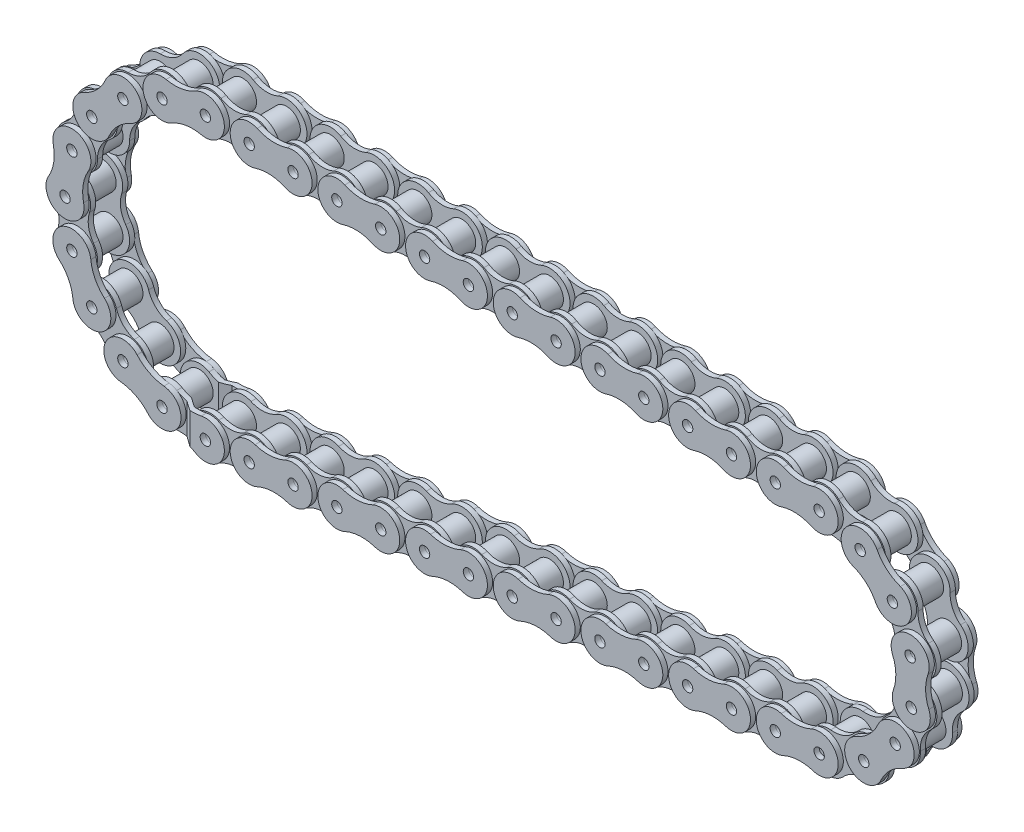
SolidWorks part; units mm, degrees
material "SUS304"
ref_plane "Front Plane" through (0, 0, 0) normal (0, 0, 1) x (1, 0, 0)
ref_plane "Top Plane" through (0, 0, 0) normal (0, 1, 0) x (1, 0, 0)
ref_plane "Right Plane" through (0, 0, 0) normal (1, 0, 0) x (0, 0, -1)
sketch "Sketch1" plane through (0, 0, 0) normal (0, 0, 1) x (1, 0, 0)
  line L0 (2.3431, 40.5223) -> (175.8629, 30.4891)
  line L1 (175.8629, -30.4891) -> (2.3431, -40.5223)
  line L2 (0, 0) -> (174.1, 0) construction
  arc A0 (2.3431, 40.5223) -> (2.3431, -40.5223) centre (0, 0) ccw
  arc A1 (175.8629, -30.4891) -> (175.8629, 30.4891) centre (174.1, 0) ccw
  dimension "D1" = 81.18
  dimension "D2" = 61.08
  dimension "D3" = 174.1
sketch "Sketch4" plane through (0, 0, 0) normal (0, 0, 1) x (1, 0, 0)
  line L1 (2.3431, 40.5223) -> (175.8629, 30.4891) construction
  line L3 (0, 0) -> (35.7842, 0) construction
  line L4 (0, 0) -> (174.1, 0) construction
  circle A0 centre (0, -40.59) radius 4
  arc A1 (2.3431, 40.5223) -> (2.3431, -40.5223) centre (0, 0) ccw construction
  circle A2 centre (-12.543, -38.6034) radius 4
  circle A3 centre (-23.8582, -32.838) radius 4
  circle A4 centre (-32.838, -23.8582) radius 4
  circle A5 centre (-38.6034, -12.543) radius 4
  circle A6 centre (-40.59, 0) radius 4
  circle A7 centre (-38.6034, 12.543) radius 4
  circle A8 centre (-32.838, 23.8582) radius 4
  circle A9 centre (-23.8582, 32.838) radius 4
  circle A10 centre (-12.543, 38.6034) radius 4
  circle A11 centre (0, 40.59) radius 4
  circle A12 centre (12.6782, 39.8618) radius 4
  circle A13 centre (25.3564, 39.1335) radius 4
  circle A14 centre (38.0345, 38.4053) radius 4
  circle A15 centre (50.7127, 37.6771) radius 4
  circle A16 centre (63.3909, 36.9488) radius 4
  circle A17 centre (76.0691, 36.2206) radius 4
  circle A18 centre (88.7473, 35.4924) radius 4
  circle A19 centre (101.4254, 34.7641) radius 4
  circle A20 centre (114.1036, 34.0359) radius 4
  circle A21 centre (126.7818, 33.3077) radius 4
  circle A22 centre (139.46, 32.5794) radius 4
  circle A23 centre (152.1382, 31.8512) radius 4
  circle A24 centre (164.8163, 31.123) radius 4
  circle A25 centre (177.4945, 30.3947) radius 4
  circle A26 centre (189.3571, 26.5029) radius 4
  circle A27 centre (198.6735, 18.192) radius 4
  circle A28 centre (203.8891, 6.8491) radius 4
  circle A29 centre (204.1336, -5.6332) radius 4
  circle A30 centre (199.3662, -17.1717) radius 4
  circle A31 centre (190.3823, -25.841) radius 4
  circle A34 centre (164.8163, -31.123) radius 4
  circle A35 centre (152.1382, -31.8512) radius 4
  circle A36 centre (139.46, -32.5794) radius 4
  circle A37 centre (126.7818, -33.3077) radius 4
  circle A38 centre (114.1036, -34.0359) radius 4
  circle A39 centre (101.4254, -34.7641) radius 4
  circle A40 centre (88.7473, -35.4924) radius 4
  circle A41 centre (76.0691, -36.2206) radius 4
  circle A42 centre (63.3909, -36.9488) radius 4
  circle A43 centre (50.7127, -37.6771) radius 4
  circle A44 centre (38.0345, -38.4053) radius 4
  circle A45 centre (25.3564, -39.1335) radius 4
  circle A46 centre (12.6782, -39.8618) radius 4
  circle A47 centre (0, -40.59) radius 4
  circle A48 centre (178.6813, -30.1944) radius 4
  arc A49 (175.8629, -30.4891) -> (175.8629, 30.4891) centre (174.1, 0) ccw construction
  dimension "D1" = 12.6993
  dimension "D3" = 8
  dimension "D5" = 12.6991
  dimension "D2" = 11
  dimension "D4" = 15
extrude "Boss-Extrude1" add sketch "Sketch4" along normal mid plane 7.8 contours A10 | A11 | A20 | A21 | A35 | A38 | A39 | A46 | A12 | A13 | A14 | A15 | A16 | A17 | A18 | A19 | A22 | A23 | A24 | A25 | A34 | A36 | A37 | A40 | A41 | A42 | A43 | A44 | A45 | A0 | A2 | A3 | A4 | A5 | A6 | A7 | A8 | A9 | A26 | A27 | A28 | A29 | A30 | A31 | A48 region at (-12.543, 38.6034, 0) region at (0, 40.59, 0) region at (114.1036, 34.0359, 0) region at (126.7818, 33.3077, 0) region at (152.1382, -31.8512, 0) region at (114.1036, -34.0359, 0) region at (101.4254, -34.7641, 0) region at (12.6782, -39.8618, 0)
sketch "Sketch5" plane through (0, 0, 3.9) normal (0, 0, 1) x (1, 0, 0)
  line L0 (0, 40.59) -> (12.6782, 39.8618) construction
  line L1 (25.3564, 39.1335) -> (38.0345, 38.4053) construction
  line L2 (50.7127, 37.6771) -> (63.3909, 36.9488) construction
  line L3 (76.0691, 36.2206) -> (88.7473, 35.4924) construction
  line L4 (101.4254, 34.7641) -> (114.1036, 34.0359) construction
  line L5 (126.7818, 33.3077) -> (139.46, 32.5794) construction
  line L6 (152.1382, 31.8512) -> (164.8163, 31.123) construction
  line L7 (0, 0) -> (224.3217, 0) construction
  line L8 (152.1382, -31.8512) -> (164.8163, -31.123) construction
  line L9 (126.7818, -33.3077) -> (139.46, -32.5794) construction
  line L10 (101.4254, -34.7641) -> (114.1036, -34.0359) construction
  line L11 (76.0691, -36.2206) -> (88.7473, -35.4924) construction
  line L12 (50.7127, -37.6771) -> (63.3909, -36.9488) construction
  line L13 (25.3564, -39.1335) -> (38.0345, -38.4053) construction
  line L14 (0, -40.59) -> (12.6782, -39.8618) construction
  line L15 (189.3571, 26.5029) -> (177.4945, 30.3947) construction
  line L16 (203.8891, 6.8491) -> (198.6735, 18.192) construction
  line L17 (199.3662, -17.1717) -> (204.1336, -5.6332) construction
  line L18 (178.6813, -30.1944) -> (190.3823, -25.841) construction
  arc A0 (2.9917, 45.6753) -> (2.3897, 35.1956) centre (0, 40.59) ccw
  arc A1 (9.6865, 34.7765) -> (10.2885, 45.2561) centre (12.6782, 39.8618) ccw
  arc A2 (2.9917, 45.6753) -> (10.2885, 45.2561) centre (7.0482, 52.5705) ccw
  arc A3 (2.3897, 35.1956) -> (9.6865, 34.7765) centre (5.63, 27.8812) cw
  circle A4 centre (0, 40.59) radius 1.5
  circle A5 centre (12.6782, 39.8618) radius 1.5
  arc A6 (28.348, 44.2188) -> (27.7461, 33.7392) centre (25.3564, 39.1335) ccw
  arc A7 (35.0429, 33.32) -> (35.6448, 43.7997) centre (38.0345, 38.4053) ccw
  arc A8 (28.348, 44.2188) -> (35.6448, 43.7997) centre (32.4045, 51.1141) ccw
  arc A9 (27.7461, 33.7392) -> (35.0429, 33.32) centre (30.9864, 26.4248) cw
  circle A10 centre (25.3564, 39.1335) radius 1.5
  circle A11 centre (38.0345, 38.4053) radius 1.5
  arc A12 (53.7044, 42.7623) -> (53.1024, 32.2827) centre (50.7127, 37.6771) ccw
  arc A13 (60.3992, 31.8636) -> (61.0012, 42.3432) centre (63.3909, 36.9488) ccw
  arc A14 (53.7044, 42.7623) -> (61.0012, 42.3432) centre (57.7609, 49.6576) ccw
  arc A15 (53.1024, 32.2827) -> (60.3992, 31.8636) centre (56.3427, 24.9683) cw
  circle A16 centre (50.7127, 37.6771) radius 1.5
  circle A17 centre (63.3909, 36.9488) radius 1.5
  arc A18 (79.0608, 41.3059) -> (78.4588, 30.8262) centre (76.0691, 36.2206) ccw
  arc A19 (85.7556, 30.4071) -> (86.3575, 40.8867) centre (88.7473, 35.4924) ccw
  arc A20 (79.0608, 41.3059) -> (86.3575, 40.8867) centre (83.1172, 48.2011) ccw
  arc A21 (78.4588, 30.8262) -> (85.7556, 30.4071) centre (81.6991, 23.5118) cw
  circle A22 centre (76.0691, 36.2206) radius 1.5
  circle A23 centre (88.7473, 35.4924) radius 1.5
  arc A24 (104.4171, 39.8494) -> (103.8152, 29.3698) centre (101.4254, 34.7641) ccw
  arc A25 (111.112, 28.9506) -> (111.7139, 39.4303) centre (114.1036, 34.0359) ccw
  arc A26 (104.4171, 39.8494) -> (111.7139, 39.4303) centre (108.4736, 46.7447) ccw
  arc A27 (103.8152, 29.3698) -> (111.112, 28.9506) centre (107.0555, 22.0554) cw
  circle A28 centre (101.4254, 34.7641) radius 1.5
  circle A29 centre (114.1036, 34.0359) radius 1.5
  arc A30 (129.7735, 38.3929) -> (129.1715, 27.9133) centre (126.7818, 33.3077) ccw
  arc A31 (136.4683, 27.4942) -> (137.0703, 37.9738) centre (139.46, 32.5794) ccw
  arc A32 (129.7735, 38.3929) -> (137.0703, 37.9738) centre (133.83, 45.2882) ccw
  arc A33 (129.1715, 27.9133) -> (136.4683, 27.4942) centre (132.4118, 20.5989) cw
  circle A34 centre (126.7818, 33.3077) radius 1.5
  circle A35 centre (139.46, 32.5794) radius 1.5
  arc A36 (155.1298, 36.9365) -> (154.5279, 26.4568) centre (152.1382, 31.8512) ccw
  arc A37 (161.8247, 26.0377) -> (162.4266, 36.5173) centre (164.8163, 31.123) ccw
  arc A38 (155.1298, 36.9365) -> (162.4266, 36.5173) centre (159.1863, 43.8317) ccw
  arc A39 (154.5279, 26.4568) -> (161.8247, 26.0377) centre (157.7682, 19.1424) cw
  circle A40 centre (152.1382, 31.8512) radius 1.5
  circle A41 centre (164.8163, 31.123) radius 1.5
  circle A42 centre (164.8163, 31.123) radius 4 construction
  circle A43 centre (164.8163, -31.123) radius 1.5
  circle A44 centre (152.1382, -31.8512) radius 1.5
  arc A45 (154.5279, -26.4568) -> (161.8247, -26.0377) centre (157.7682, -19.1424) ccw
  arc A46 (155.1298, -36.9365) -> (162.4266, -36.5173) centre (159.1863, -43.8317) cw
  arc A47 (161.8247, -26.0377) -> (162.4266, -36.5173) centre (164.8163, -31.123) cw
  arc A48 (155.1298, -36.9365) -> (154.5279, -26.4568) centre (152.1382, -31.8512) cw
  circle A49 centre (139.46, -32.5794) radius 1.5
  circle A50 centre (126.7818, -33.3077) radius 1.5
  arc A51 (129.1715, -27.9133) -> (136.4683, -27.4942) centre (132.4118, -20.5989) ccw
  arc A52 (129.7735, -38.3929) -> (137.0703, -37.9738) centre (133.83, -45.2882) cw
  arc A53 (136.4683, -27.4942) -> (137.0703, -37.9738) centre (139.46, -32.5794) cw
  arc A54 (129.7735, -38.3929) -> (129.1715, -27.9133) centre (126.7818, -33.3077) cw
  circle A55 centre (114.1036, -34.0359) radius 1.5
  circle A56 centre (101.4254, -34.7641) radius 1.5
  arc A57 (103.8152, -29.3698) -> (111.112, -28.9506) centre (107.0555, -22.0554) ccw
  arc A58 (104.4171, -39.8494) -> (111.7139, -39.4303) centre (108.4736, -46.7447) cw
  arc A59 (111.112, -28.9506) -> (111.7139, -39.4303) centre (114.1036, -34.0359) cw
  arc A60 (104.4171, -39.8494) -> (103.8152, -29.3698) centre (101.4254, -34.7641) cw
  circle A61 centre (88.7473, -35.4924) radius 1.5
  circle A62 centre (76.0691, -36.2206) radius 1.5
  arc A63 (78.4588, -30.8262) -> (85.7556, -30.4071) centre (81.6991, -23.5118) ccw
  arc A64 (79.0608, -41.3059) -> (86.3575, -40.8867) centre (83.1172, -48.2011) cw
  arc A65 (85.7556, -30.4071) -> (86.3575, -40.8867) centre (88.7473, -35.4924) cw
  arc A66 (79.0608, -41.3059) -> (78.4588, -30.8262) centre (76.0691, -36.2206) cw
  circle A67 centre (63.3909, -36.9488) radius 1.5
  circle A68 centre (50.7127, -37.6771) radius 1.5
  arc A69 (53.1024, -32.2827) -> (60.3992, -31.8636) centre (56.3427, -24.9683) ccw
  arc A70 (53.7044, -42.7623) -> (61.0012, -42.3432) centre (57.7609, -49.6576) cw
  arc A71 (60.3992, -31.8636) -> (61.0012, -42.3432) centre (63.3909, -36.9488) cw
  arc A72 (53.7044, -42.7623) -> (53.1024, -32.2827) centre (50.7127, -37.6771) cw
  circle A73 centre (38.0345, -38.4053) radius 1.5
  circle A74 centre (25.3564, -39.1335) radius 1.5
  arc A75 (27.7461, -33.7392) -> (35.0429, -33.32) centre (30.9864, -26.4248) ccw
  arc A76 (28.348, -44.2188) -> (35.6448, -43.7997) centre (32.4045, -51.1141) cw
  arc A77 (35.0429, -33.32) -> (35.6448, -43.7997) centre (38.0345, -38.4053) cw
  arc A78 (28.348, -44.2188) -> (27.7461, -33.7392) centre (25.3564, -39.1335) cw
  circle A79 centre (12.6782, -39.8618) radius 1.5
  circle A80 centre (0, -40.59) radius 1.5
  arc A81 (2.3897, -35.1956) -> (9.6865, -34.7765) centre (5.63, -27.8812) ccw
  arc A82 (2.9917, -45.6753) -> (10.2885, -45.2561) centre (7.0482, -52.5705) cw
  arc A83 (9.6865, -34.7765) -> (10.2885, -45.2561) centre (12.6782, -39.8618) cw
  arc A84 (2.9917, -45.6753) -> (2.3897, -35.1956) centre (0, -40.59) cw
  arc A85 (181.6554, 34.5777) -> (178.3688, 24.5599) centre (177.4945, 30.3947) ccw
  arc A86 (185.1962, 22.32) -> (188.4828, 32.3378) centre (189.3571, 26.5029) ccw
  arc A87 (181.6554, 34.5777) -> (188.4828, 32.3378) centre (187.2973, 40.2494) ccw
  arc A88 (178.3688, 24.5599) -> (185.1962, 22.32) centre (179.5543, 16.6482) cw
  circle A89 centre (177.4945, 30.3947) radius 1.5
  circle A90 centre (189.3571, 26.5029) radius 1.5
  arc A91 (204.5699, 17.987) -> (194.9909, 13.5824) centre (198.6735, 18.192) ccw
  arc A92 (197.9927, 7.0541) -> (207.5717, 11.4587) centre (203.8891, 6.8491) ccw
  arc A93 (204.5699, 17.987) -> (207.5717, 11.4587) centre (212.5651, 17.709) ccw
  arc A94 (194.9909, 13.5824) -> (197.9927, 7.0541) centre (189.9975, 7.3321) cw
  circle A95 centre (198.6735, 18.192) radius 1.5
  circle A96 centre (203.8891, 6.8491) radius 1.5
  arc A97 (207.9939, -10.095) -> (198.2498, -6.069) centre (204.1336, -5.6332) ccw
  arc A98 (195.5059, -12.7099) -> (205.2501, -16.7359) centre (199.3662, -17.1717) ccw
  arc A99 (207.9939, -10.095) -> (205.2501, -16.7359) centre (213.2282, -16.145) ccw
  arc A100 (198.2498, -6.069) -> (195.5059, -12.7099) centre (190.2716, -6.6599) cw
  circle A101 centre (204.1336, -5.6332) radius 1.5
  circle A102 centre (199.3662, -17.1717) radius 1.5
  arc A103 (189.7372, -31.7056) -> (186.0608, -21.8242) centre (190.3823, -25.841) ccw
  arc A104 (179.3264, -24.3298) -> (183.0028, -34.2112) centre (178.6813, -30.1944) ccw
  arc A105 (189.7372, -31.7056) -> (183.0028, -34.2112) centre (188.8625, -39.6577) ccw
  arc A106 (186.0608, -21.8242) -> (179.3264, -24.3298) centre (180.2012, -16.3778) cw
  circle A107 centre (190.3823, -25.841) radius 1.5
  circle A108 centre (178.6813, -30.1944) radius 1.5
  arc A110 (175.8629, -30.4891) -> (175.8629, 30.4891) centre (174.1, 0) ccw construction
  circle A111 centre (198.6735, 18.192) radius 4 construction
  arc A113 (-12.5617, 32.7034) -> (-17.3272, 42.0562) centre (-12.543, 38.6034) ccw
  circle A114 centre (-12.543, 38.6034) radius 1.5
  circle A115 centre (-23.8582, 32.838) radius 1.5
  arc A116 (-23.8395, 38.738) -> (-19.074, 29.3852) centre (-23.8582, 32.838) ccw
  arc A117 (-17.3272, 42.0562) -> (-23.8395, 38.738) centre (-23.8142, 46.7379) cw
  arc A118 (-12.5617, 32.7034) -> (-19.074, 29.3852) centre (-12.587, 24.7035) ccw
  arc A119 (-29.3852, 19.074) -> (-38.738, 23.8395) centre (-32.838, 23.8582) ccw
  circle A120 centre (-32.838, 23.8582) radius 1.5
  circle A121 centre (-38.6034, 12.543) radius 1.5
  arc A122 (-42.0562, 17.3272) -> (-32.7034, 12.5617) centre (-38.6034, 12.543) ccw
  arc A123 (-38.738, 23.8395) -> (-42.0562, 17.3272) centre (-46.7379, 23.8142) cw
  arc A124 (-29.3852, 19.074) -> (-32.7034, 12.5617) centre (-24.7035, 12.587) ccw
  arc A125 (-34.9846, -1.841) -> (-45.3522, -3.483) centre (-40.59, 0) ccw
  circle A126 centre (-40.59, 0) radius 1.5
  circle A127 centre (-38.6034, -12.543) radius 1.5
  arc A128 (-44.2088, -10.702) -> (-33.8412, -9.06) centre (-38.6034, -12.543) ccw
  arc A129 (-45.3522, -3.483) -> (-44.2088, -10.702) centre (-51.8094, -8.2058) cw
  arc A130 (-34.9846, -1.841) -> (-33.8412, -9.06) centre (-27.384, -4.3372) ccw
  arc A131 (-27.221, -22.0528) -> (-34.6434, -29.4752) centre (-32.838, -23.8582) ccw
  circle A132 centre (-32.838, -23.8582) radius 1.5
  circle A133 centre (-23.8582, -32.838) radius 1.5
  arc A134 (-29.4752, -34.6434) -> (-22.0528, -27.221) centre (-23.8582, -32.838) ccw
  arc A135 (-34.6434, -29.4752) -> (-29.4752, -34.6434) centre (-37.0914, -37.0914) cw
  arc A136 (-27.221, -22.0528) -> (-22.0528, -27.221) centre (-19.6048, -19.6048) ccw
  circle A137 centre (-23.8582, -32.838) radius 4 construction
  arc A138 (2.3431, 40.5223) -> (2.3431, -40.5223) centre (0, 0) ccw construction
  dimension "D1" = 11.8
  dimension "D2" = 8
  dimension "D3" = 3
  dimension "D5" = 8
  dimension "D4" = 7
extrude "Boss-Extrude2" add sketch "Sketch5" along normal blind 1.5 separate body
sketch "Sketch6" plane through (0, 0, 5.4) normal (0, 0, 1) x (1, 0, 0)
  line L0 (0, 0) -> (23.0702, 0) construction
  arc A0 (-11.3737, 43.9777) -> (-9.7702, 33.8535) centre (-12.543, 38.6034) ccw
  arc A1 (-1.1693, 35.2157) -> (-2.7728, 45.3399) centre (0, 40.59) ccw
  arc A2 (-2.7728, 45.3399) -> (-11.3737, 43.9777) centre (-8.8225, 55.7033) cw
  arc A3 (-1.1693, 35.2157) -> (-9.7702, 33.8535) centre (-3.7205, 23.4901) ccw
  circle A4 centre (0, 40.59) radius 1.5 construction
  circle A5 centre (-12.543, 38.6034) radius 1.5 construction
  circle A6 centre (0, 40.59) radius 1.5
  circle A7 centre (-12.543, 38.6034) radius 1.5
  arc A8 (14.9644, 44.8641) -> (14.3766, 34.6306) centre (12.6782, 39.8618) ccw
  arc A9 (23.0702, 34.1312) -> (23.658, 44.3647) centre (25.3564, 39.1335) ccw
  arc A10 (23.658, 44.3647) -> (14.9644, 44.8641) centre (19.9524, 55.7783) cw
  arc A11 (23.0702, 34.1312) -> (14.3766, 34.6306) centre (18.0821, 23.217) ccw
  circle A12 centre (25.3564, 39.1335) radius 1.5
  circle A13 centre (12.6782, 39.8618) radius 1.5
  circle A14 centre (25.3564, 39.1335) radius 1.5 construction
  arc A15 (40.3207, 43.4076) -> (39.7329, 33.1741) centre (38.0345, 38.4053) ccw
  arc A16 (48.4265, 32.6747) -> (49.0143, 42.9083) centre (50.7127, 37.6771) ccw
  arc A17 (49.0143, 42.9083) -> (40.3207, 43.4076) centre (45.3088, 54.3218) cw
  arc A18 (48.4265, 32.6747) -> (39.7329, 33.1741) centre (43.4385, 21.7606) ccw
  circle A19 centre (50.7127, 37.6771) radius 1.5
  circle A20 centre (38.0345, 38.4053) radius 1.5
  arc A21 (65.6771, 41.9512) -> (65.0893, 31.7176) centre (63.3909, 36.9488) ccw
  arc A22 (73.7829, 31.2183) -> (74.3707, 41.4518) centre (76.0691, 36.2206) ccw
  arc A23 (74.3707, 41.4518) -> (65.6771, 41.9512) centre (70.6651, 52.8653) cw
  arc A24 (73.7829, 31.2183) -> (65.0893, 31.7176) centre (68.7948, 20.3041) ccw
  circle A25 centre (76.0691, 36.2206) radius 1.5
  circle A26 centre (63.3909, 36.9488) radius 1.5
  arc A27 (91.0335, 40.4947) -> (90.4456, 30.2612) centre (88.7473, 35.4924) ccw
  arc A28 (99.1393, 29.7618) -> (99.7271, 39.9953) centre (101.4254, 34.7641) ccw
  arc A29 (99.7271, 39.9953) -> (91.0335, 40.4947) centre (96.0215, 51.4089) cw
  arc A30 (99.1393, 29.7618) -> (90.4456, 30.2612) centre (94.1512, 18.8476) ccw
  circle A31 centre (101.4254, 34.7641) radius 1.5
  circle A32 centre (88.7473, 35.4924) radius 1.5
  arc A33 (116.3898, 39.0382) -> (115.802, 28.8047) centre (114.1036, 34.0359) ccw
  arc A34 (124.4956, 28.3053) -> (125.0834, 38.5389) centre (126.7818, 33.3077) ccw
  arc A35 (125.0834, 38.5389) -> (116.3898, 39.0382) centre (121.3779, 49.9524) cw
  arc A36 (124.4956, 28.3053) -> (115.802, 28.8047) centre (119.5076, 17.3912) ccw
  circle A37 centre (126.7818, 33.3077) radius 1.5
  circle A38 centre (114.1036, 34.0359) radius 1.5
  arc A39 (141.7462, 37.5818) -> (141.1584, 27.3482) centre (139.46, 32.5794) ccw
  arc A40 (149.852, 26.8489) -> (150.4398, 37.0824) centre (152.1382, 31.8512) ccw
  arc A41 (150.4398, 37.0824) -> (141.7462, 37.5818) centre (146.7342, 48.4959) cw
  arc A42 (149.852, 26.8489) -> (141.1584, 27.3482) centre (144.8639, 15.9347) ccw
  circle A43 centre (152.1382, 31.8512) radius 1.5
  circle A44 centre (139.46, 32.5794) radius 1.5
  arc A45 (167.1025, 36.1253) -> (166.5147, 25.8918) centre (164.8163, 31.123) ccw
  arc A46 (175.2083, 25.3924) -> (175.7961, 35.6259) centre (177.4945, 30.3947) ccw
  arc A47 (175.7961, 35.6259) -> (167.1025, 36.1253) centre (172.0906, 47.0395) cw
  arc A48 (175.2083, 25.3924) -> (166.5147, 25.8918) centre (170.2203, 14.4782) ccw
  circle A49 centre (177.4945, 30.3947) radius 1.5
  circle A50 centre (164.8163, 31.123) radius 1.5
  circle A51 centre (177.4945, 30.3947) radius 1.5 construction
  circle A52 centre (164.8163, -31.123) radius 1.5
  circle A53 centre (177.4945, -30.3947) radius 1.5
  arc A54 (175.2083, -25.3924) -> (166.5147, -25.8918) centre (170.2203, -14.4782) cw
  arc A55 (175.7961, -35.6259) -> (167.1025, -36.1253) centre (172.0906, -47.0395) ccw
  arc A56 (175.2083, -25.3924) -> (175.7961, -35.6259) centre (177.4945, -30.3947) cw
  arc A57 (167.1025, -36.1253) -> (166.5147, -25.8918) centre (164.8163, -31.123) cw
  circle A58 centre (139.46, -32.5794) radius 1.5
  circle A59 centre (152.1382, -31.8512) radius 1.5
  arc A60 (149.852, -26.8489) -> (141.1584, -27.3482) centre (144.8639, -15.9347) cw
  arc A61 (150.4398, -37.0824) -> (141.7462, -37.5818) centre (146.7342, -48.4959) ccw
  arc A62 (149.852, -26.8489) -> (150.4398, -37.0824) centre (152.1382, -31.8512) cw
  arc A63 (141.7462, -37.5818) -> (141.1584, -27.3482) centre (139.46, -32.5794) cw
  circle A64 centre (114.1036, -34.0359) radius 1.5
  circle A65 centre (126.7818, -33.3077) radius 1.5
  arc A66 (124.4956, -28.3053) -> (115.802, -28.8047) centre (119.5076, -17.3912) cw
  arc A67 (125.0834, -38.5389) -> (116.3898, -39.0382) centre (121.3779, -49.9524) ccw
  arc A68 (124.4956, -28.3053) -> (125.0834, -38.5389) centre (126.7818, -33.3077) cw
  arc A69 (116.3898, -39.0382) -> (115.802, -28.8047) centre (114.1036, -34.0359) cw
  circle A70 centre (88.7473, -35.4924) radius 1.5
  circle A71 centre (101.4254, -34.7641) radius 1.5
  arc A72 (99.1393, -29.7618) -> (90.4456, -30.2612) centre (94.1512, -18.8476) cw
  arc A73 (99.7271, -39.9953) -> (91.0335, -40.4947) centre (96.0215, -51.4089) ccw
  arc A74 (99.1393, -29.7618) -> (99.7271, -39.9953) centre (101.4254, -34.7641) cw
  arc A75 (91.0335, -40.4947) -> (90.4456, -30.2612) centre (88.7473, -35.4924) cw
  circle A76 centre (63.3909, -36.9488) radius 1.5
  circle A77 centre (76.0691, -36.2206) radius 1.5
  arc A78 (73.7829, -31.2183) -> (65.0893, -31.7176) centre (68.7948, -20.3041) cw
  arc A79 (74.3707, -41.4518) -> (65.6771, -41.9512) centre (70.6651, -52.8653) ccw
  arc A80 (73.7829, -31.2183) -> (74.3707, -41.4518) centre (76.0691, -36.2206) cw
  arc A81 (65.6771, -41.9512) -> (65.0893, -31.7176) centre (63.3909, -36.9488) cw
  circle A82 centre (38.0345, -38.4053) radius 1.5
  circle A83 centre (50.7127, -37.6771) radius 1.5
  arc A84 (48.4265, -32.6747) -> (39.7329, -33.1741) centre (43.4385, -21.7606) cw
  arc A85 (49.0143, -42.9083) -> (40.3207, -43.4076) centre (45.3088, -54.3218) ccw
  arc A86 (48.4265, -32.6747) -> (49.0143, -42.9083) centre (50.7127, -37.6771) cw
  arc A87 (40.3207, -43.4076) -> (39.7329, -33.1741) centre (38.0345, -38.4053) cw
  circle A88 centre (12.6782, -39.8618) radius 1.5
  circle A89 centre (25.3564, -39.1335) radius 1.5
  arc A90 (23.0702, -34.1312) -> (14.3766, -34.6306) centre (18.0821, -23.217) cw
  arc A91 (23.658, -44.3647) -> (14.9644, -44.8641) centre (19.9524, -55.7783) ccw
  arc A92 (23.0702, -34.1312) -> (23.658, -44.3647) centre (25.3564, -39.1335) cw
  arc A93 (14.9644, -44.8641) -> (14.3766, -34.6306) centre (12.6782, -39.8618) cw
  arc A94 (194.246, 29.0225) -> (187.0636, 21.5039) centre (189.3571, 26.5029) ccw
  arc A95 (193.9322, 15.4046) -> (201.0016, 23.175) centre (198.6735, 18.192) ccw
  arc A96 (201.0016, 23.175) -> (194.246, 29.0225) centre (204.9128, 34.5197) cw
  arc A97 (193.9322, 15.4046) -> (187.0636, 21.5039) centre (183.1367, 10.1646) ccw
  circle A98 centre (198.6735, 18.192) radius 1.5
  circle A99 centre (189.3571, 26.5029) radius 1.5
  arc A100 (201.6271, -22.0479) -> (194.4774, -14.7026) centre (199.4822, -16.9833) ccw
  arc A101 (188.2375, -20.7765) -> (195.3872, -28.1217) centre (190.3823, -25.841) ccw
  arc A102 (195.3872, -28.1217) -> (201.6271, -22.0479) centre (206.3069, -33.0978) cw
  arc A103 (188.2375, -20.7765) -> (194.4774, -14.7026) centre (183.5577, -9.7266) ccw
  circle A104 centre (190.3823, -25.841) radius 1.5
  circle A105 centre (199.4822, -16.9833) radius 1.5
  arc A106 (189.7372, -31.7056) -> (186.0608, -21.8242) centre (190.3823, -25.841) ccw construction
  arc A107 (175.8629, -30.4891) -> (175.8629, 30.4891) centre (174.1, 0) ccw construction
  arc A108 (203.3416, 18.301) -> (193.7384, 14.7163) centre (197.8421, 18.3782) ccw [skipped]
  arc A109 (196.7837, 6.5582) -> (206.3869, 10.1429) centre (202.2832, 6.481) ccw [skipped]
  arc A110 (206.3869, 10.1429) -> (203.3416, 18.301) centre (215.3404, 18.1326) cw [skipped]
  arc A111 (196.7837, 6.5582) -> (193.7384, 14.7163) centre (184.7849, 6.7266) ccw [skipped]
  circle A112 centre (202.2832, 6.481) radius 1.5 [skipped]
  circle A113 centre (197.8421, 18.3782) radius 1.5 [skipped]
  arc A114 (208.9864, 5.1966) -> (198.7393, 4.9372) centre (203.8123, 7.0618) ccw
  arc A115 (198.9596, -3.7679) -> (209.2067, -3.5086) centre (204.1336, -5.6332) ccw
  arc A116 (209.2067, -3.5086) -> (208.9864, 5.1966) centre (220.2752, 1.1269) cw
  arc A117 (198.9596, -3.7679) -> (198.7393, 4.9372) centre (187.6707, 0.3017) ccw
  circle A118 centre (204.1336, -5.6332) radius 1.5
  circle A119 centre (203.8123, 7.0618) radius 1.5
  arc A120 (207.9939, -10.095) -> (198.2498, -6.069) centre (204.1336, -5.6332) ccw construction
  circle A121 centre (198.6735, 18.192) radius 1.5 construction
  circle A122 centre (189.3571, 26.5029) radius 1.5 construction
  arc A123 (-35.0509, 28.8934) -> (-27.8028, 21.6453) centre (-32.838, 23.8582) ccw
  arc A124 (-21.6453, 27.8028) -> (-28.8934, 35.0509) centre (-23.8582, 32.838) ccw
  arc A125 (-28.8934, 35.0509) -> (-35.0509, 28.8934) centre (-39.8792, 39.8792) cw
  arc A126 (-21.6453, 27.8028) -> (-27.8028, 21.6453) centre (-16.817, 16.817) ccw
  circle A127 centre (-23.8582, 32.838) radius 1.5
  circle A128 centre (-32.838, 23.8582) radius 1.5
  arc A129 (-45.3399, 2.7728) -> (-35.2157, 1.1693) centre (-40.59, 0) ccw
  arc A130 (-33.8535, 9.7702) -> (-43.9777, 11.3737) centre (-38.6034, 12.543) ccw
  arc A131 (-43.9777, 11.3737) -> (-45.3399, 2.7728) centre (-55.7033, 8.8225) cw
  arc A132 (-33.8535, 9.7702) -> (-35.2157, 1.1693) centre (-23.4901, 3.7205) ccw
  circle A133 centre (-38.6034, 12.543) radius 1.5
  circle A134 centre (-40.59, 0) radius 1.5
  arc A135 (-38.3106, -24.4069) -> (-29.1774, -19.7533) centre (-32.838, -23.8582) ccw
  arc A136 (-33.1308, -11.9943) -> (-42.264, -16.6479) centre (-38.6034, -12.543) ccw
  arc A137 (-42.264, -16.6479) -> (-38.3106, -24.4069) centre (-50.2507, -25.604) cw
  arc A138 (-33.1308, -11.9943) -> (-29.1774, -19.7533) centre (-21.1907, -10.7972) ccw
  circle A139 centre (-38.6034, -12.543) radius 1.5
  circle A140 centre (-32.838, -23.8582) radius 1.5
  arc A141 (-16.6479, -42.264) -> (-11.9943, -33.1308) centre (-12.543, -38.6034) ccw
  arc A142 (-19.7533, -29.1774) -> (-24.4069, -38.3106) centre (-23.8582, -32.838) ccw
  arc A143 (-24.4069, -38.3106) -> (-16.6479, -42.264) centre (-25.604, -50.2507) cw
  arc A144 (-19.7533, -29.1774) -> (-11.9943, -33.1308) centre (-10.7972, -21.1907) ccw
  circle A145 centre (-23.8582, -32.838) radius 1.5
  circle A146 centre (-12.543, -38.6034) radius 1.5
  arc A147 (-23.8395, 38.738) -> (-19.074, 29.3852) centre (-23.8582, 32.838) ccw construction
  arc A148 (2.3431, 40.5223) -> (2.3431, -40.5223) centre (0, 0) ccw construction
  dimension "D1" = 11
  dimension "D2" = 12
  dimension "D3" = 7
extrude "Boss-Extrude3" add sketch "Sketch6" along normal blind 1.5 separate body
mirror "Mirror2" about plane through (0, 0, 0) normal (0, 0, 1) of bodies 228 227 229 230 231 232 233 234 242 244 243 235 236 237 238 239 240 241 196 248 247 246 245 189 188 187 186 185 184 183 201 202 203 204 195 194 193 192 197 198
ref_axis "Axis1" through (0, 0, -7.59) along (0, 0, 1)
sketch "Sketch7" plane through (0, 0, -5.4) normal (0, 0, -1) x (-1, 0, 0)
  arc A0 (1.1693, -35.2157) -> (2.7728, -45.3399) centre (0, -40.59) ccw
  arc A1 (11.3737, -43.9777) -> (9.7702, -33.8535) centre (12.543, -38.6034) ccw
  circle A2 centre (0, -40.59) radius 1.5 construction
  circle A3 centre (12.543, -38.6034) radius 1.5 construction
  circle A4 centre (0, -40.59) radius 1.5
  circle A5 centre (12.543, -38.6034) radius 1.5
  arc A6 (1.1693, -35.2157) -> (9.7702, -33.8535) centre (3.7205, -23.4901) ccw
  arc A7 (11.3737, -43.9777) -> (2.7728, -45.3399) centre (8.8225, -55.7033) ccw
  arc A8 (24.4069, -38.3106) -> (19.7533, -29.1774) centre (23.8582, -32.838) ccw construction
  arc A9 (11.9943, -33.1308) -> (19.7533, -29.1774) centre (10.7972, -21.1907) ccw construction
extrude "Boss-Extrude4" add sketch "Sketch7" along normal mid plane 3 separate body
mirror "Mirror3" about plane through (0, 0, 0) normal (0, 0, 1) of bodies 293
sketch "Sketch8" plane through (0, 0, 0) normal (0, 1, 0) x (1, 0, 0)
  line L0 (6.6401, -5.4) -> (-4.6661, -5.4)
  line L1 (2.9917, -5.4) -> (10.2885, -5.4) construction
  line L2 (-5.9, -5.4) -> (2.9917, -5.4) construction
  line L3 (-4.6661, -5.4) -> (-8.8701, -2.6872)
  line L4 (-8.8701, -2.6872) -> (6.6401, -2.6872)
  line L5 (6.6401, -2.6872) -> (6.6401, -5.4)
  line L6 (-4.48, -6.9) -> (-6.8045, -5.4)
  line L7 (-11.3737, -6.9) -> (-2.7728, -6.9) construction
  line L8 (-6.8045, -5.4) -> (-20.1451, -5.4)
  line L9 (-16.6479, -5.4) -> (-24.4069, -5.4) construction
  line L10 (-20.1451, -5.4) -> (-20.1451, -8.3201)
  line L11 (-20.1451, -8.3201) -> (-4.48, -8.3201)
  line L12 (-4.48, -8.3201) -> (-4.48, -6.9)
  line L13 (0, 0) -> (4.7373, 0) construction
  line L14 (-4.48, 8.3201) -> (-4.48, 6.9)
  line L15 (-20.1451, 8.3201) -> (-4.48, 8.3201)
  line L16 (-20.1451, 5.4) -> (-20.1451, 8.3201)
  line L17 (-6.8045, 5.4) -> (-20.1451, 5.4)
  line L18 (-4.48, 6.9) -> (-6.8045, 5.4)
  line L19 (6.6401, 2.6872) -> (6.6401, 5.4)
  line L20 (-8.8701, 2.6872) -> (6.6401, 2.6872)
  line L21 (-4.6661, 5.4) -> (-8.8701, 2.6872)
  line L22 (6.6401, 5.4) -> (-4.6661, 5.4)
extrude "Cut-Extrude1" cut sketch "Sketch8" against normal blind 76
equation "\"Mass Kg\"= \"SW-Mass\""
